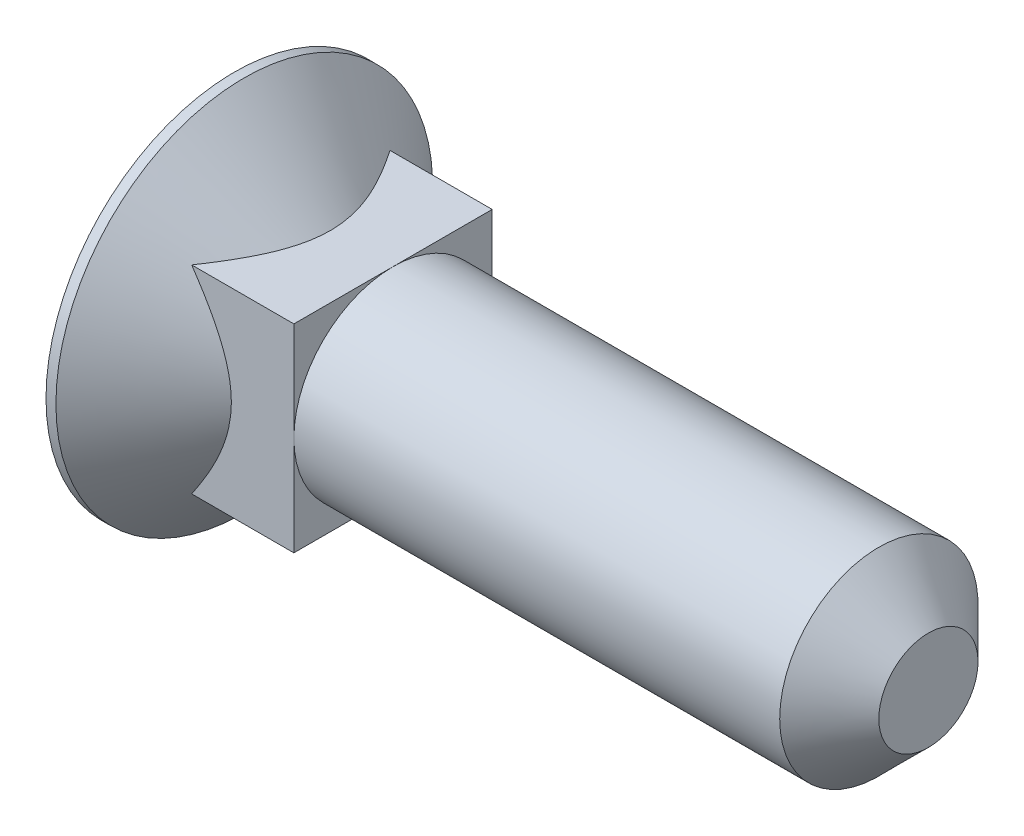
SolidWorks part; units mm, degrees
ref_plane "Front Plane" through (0, 0, 0) normal (0, 0, 1) x (1, 0, 0)
ref_plane "Top Plane" through (0, 0, 0) normal (0, 1, 0) x (1, 0, 0)
ref_plane "Right Plane" through (0, 0, 0) normal (1, 0, 0) x (0, 0, -1)
sketch "BodySke" plane through (0, 0, 0) normal (0, 0, 1) x (1, 0, 0)
  line L0 (0, 0) -> (44.1549, 0) construction
  line L1 (0, 0) -> (0, 9.5)
  line L2 (0, 9.5) -> (0.5, 9.5)
  line L3 (0.5, 9.5) -> (4.8456, 5)
  line L4 (4.8456, 5) -> (32.5, 5)
  line L5 (32.5, 5) -> (35, 2.5)
  line L6 (35, 2.5) -> (35, 0)
  line L7 (35, 0) -> (0, 0)
  line L8 (0, -9.5) -> (0.5, -9.5) construction
  line L9 (0.5, -9.5) -> (4.8456, -5) construction
  line L10 (8, 5) -> (8, 0) construction
  line L11 (33.5, 0) -> (33.5, 5) construction
  point P16 (0, 4.172)
  dimension "Thread_minor" = 8.344
  dimension "Advance" = 1.5
revolve "BaseBody" add sketch "BodySke" angle 360 about L0
cosmetic thread "ThreadCosmetic" [suppressed] parameters "Thread_minor"=8.344
sketch "SquareSke" plane through (0, 0, 0) normal (1, 0, 0) x (0, 0, -1)
  line L0 (-5, 5) -> (5, -5) construction
  line L1 (-5, 5) -> (5, 5)
  line L2 (-5, 5) -> (-5, -5)
  line L3 (-5, -5) -> (5, -5)
  line L4 (5, 5) -> (5, -5)
  dimension "D1" = 10
extrude "Square" add sketch "SquareSke" along normal blind 8
sketch "ThdSchSke" plane through (0, 0, 0) normal (0, 0, 1) x (1, 0, 0)
  line L0 (0, 0) -> (40.6405, 0) construction
  line L1 (0, 9.5) -> (0, -9.5) construction
  line L2 (31, 5.9561) -> (31, 5)
  line L3 (31, 5.9561) -> (31.9561, 5.9561)
  line L4 (31.9561, 5.9561) -> (31.9561, 5)
  line L5 (31.9561, 5) -> (31.478, 4.172)
  line L6 (31.478, 4.172) -> (31, 5)
  line L8 (4.8456, 5) -> (32.5, 5) construction
  dimension "D1" = 1.5
revolve "ThreadSchematic" [suppressed] cut sketch "ThdSchSke" angle 360 about L0
pattern_linear "ThdSchPat" [suppressed] of bodies 114
equation "\"Thread_minor@ThreadCosmetic\" = \"Thread_minor@BodySke\""
equation "\"D1@ThdSchSke\" = \"Advance@BodySke\""
equation "\"Advance@ThdSchPat\" = \"Advance@BodySke\""
equation "\"Teeth_Num@ThdSchPat\" =  int( (  \"Thread_length@BodySke\"  - \"Depth_Chamfer@BodySke\" ) / \"Advance@BodySke\" )"
equation "\"D1@SquareSke\" = \"Diameter@BodySke\""
